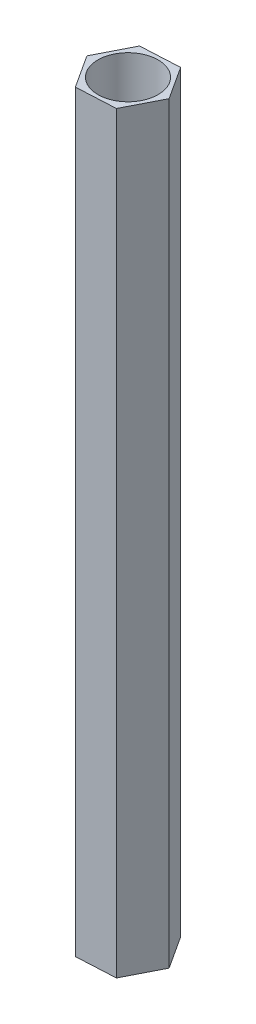
SolidWorks part; units mm, degrees
ref_plane "Front Plane" through (0, 0, 0) normal (0, 0, 1) x (1, 0, 0)
ref_plane "Top Plane" through (0, 0, 0) normal (0, 1, 0) x (1, 0, 0)
ref_plane "Right Plane" through (0, 0, 0) normal (1, 0, 0) x (0, 0, -1)
sketch "Sketch1" plane through (0, 0, 0) normal (0, 1, 0) x (1, 0, 0)
  line L1 (1.4133, -2.1801) -> (2.5946, 0.1339)
  line L2 (2.5946, 0.1339) -> (1.1813, 2.314)
  line L3 (1.1813, 2.314) -> (-1.4133, 2.1801)
  line L4 (-1.4133, 2.1801) -> (-2.5946, -0.1339)
  line L5 (-2.5946, -0.1339) -> (-1.1813, -2.314)
  line L6 (-1.1813, -2.314) -> (1.4133, -2.1801)
  circle A0 centre (0, 0) radius 2.25 construction
  circle A1 centre (0, 0) radius 2
  dimension "D1" = 4.5
  dimension "D2" = 4
extrude "Boss-Extrude1" add sketch "Sketch1" along normal blind 50
